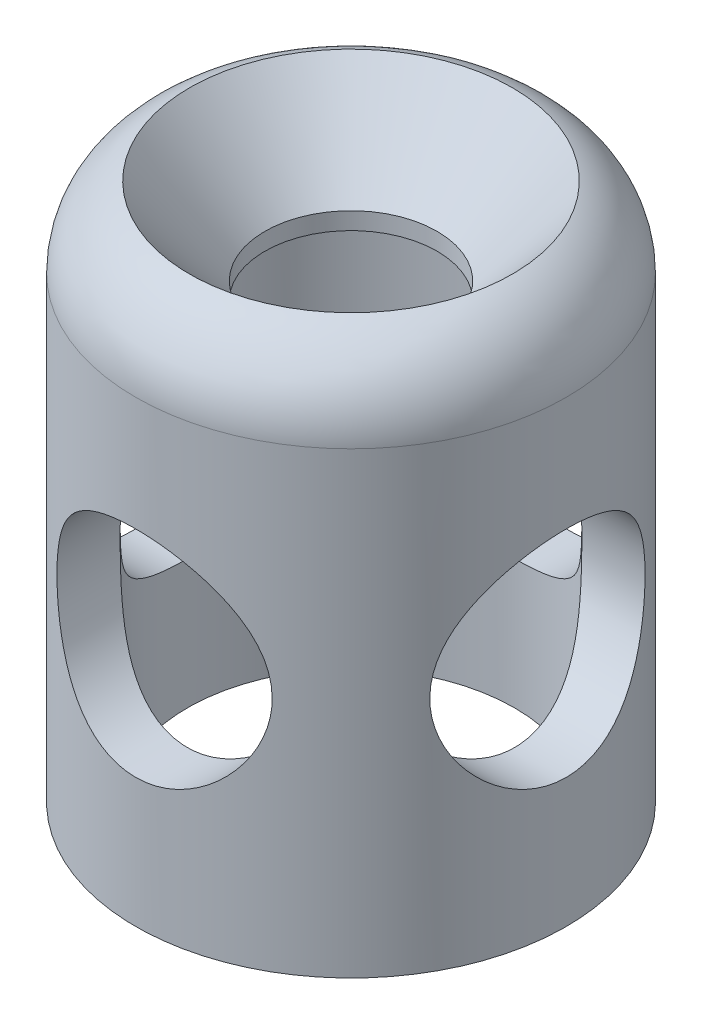
SolidWorks part; units mm, degrees
ref_plane "Front Plane" through (0, 0, 0) normal (0, 0, 1) x (1, 0, 0)
ref_plane "Top Plane" through (0, 0, 0) normal (0, 1, 0) x (1, 0, 0)
ref_plane "Right Plane" through (0, 0, 0) normal (1, 0, 0) x (0, 0, -1)
sketch "Sketch1" plane through (0, 0, 0) normal (0, 0, 1) x (1, 0, 0)
  line L0 (6.35, 0) -> (6.35, 15.875)
  line L1 (6.35, 15.875) -> (4.7625, 15.875)
  line L2 (4.7625, 15.875) -> (2.54, 13.3183)
  line L3 (2.54, 13.3183) -> (2.54, 12.8103)
  line L4 (2.54, 12.8103) -> (4.826, 12.8103)
  line L5 (4.826, 12.8103) -> (4.826, 0)
  line L6 (4.826, 0) -> (6.35, 0)
  line L7 (0, 0) -> (0, 19.9576) construction
  dimension "D1" = 4.826
  dimension "D2" = 15.875
  dimension "D3" = 6.35
  dimension "D4" = 0.508
  dimension "D5" = 4.7625
  dimension "D6" = 41
  dimension "D7" = 2.54
revolve "Revolve1" add sketch "Sketch1" angle 360 about L7
fillet "Fillet1" radius 2.54 1 edges at (0, 15.875, -6.35)
sketch "Sketch2" plane through (0, 0, 0) normal (1, 0, 0) x (0, 0, -1)
  line L0 (-6.35, 0) -> (6.35, 0) construction
  line L1 (3.175, 10.16) -> (-3.175, 10.16) construction
  line L2 (3.175, 10.16) -> (3.175, 3.81) construction
  line L3 (3.175, 3.81) -> (-3.175, 3.81) construction
  line L4 (-3.175, 10.16) -> (-3.175, 3.81) construction
  line L5 (-6.35, 13.5204) -> (-6.35, 0) construction
  circle A0 centre (0, 6.985) radius 3.175
  dimension "D1" = 6.35
  dimension "D2" = 6.35
  dimension "D3" = 3.81
  dimension "D4" = 3.175
extrude "Cut-Extrude1" cut sketch "Sketch2" against normal through all both and the other way through all
pattern_circular "CirPattern1" count 4 over 360 about axis through (0, 12.8103, 0) along (0, -1, 0) of "Cut-Extrude1"
